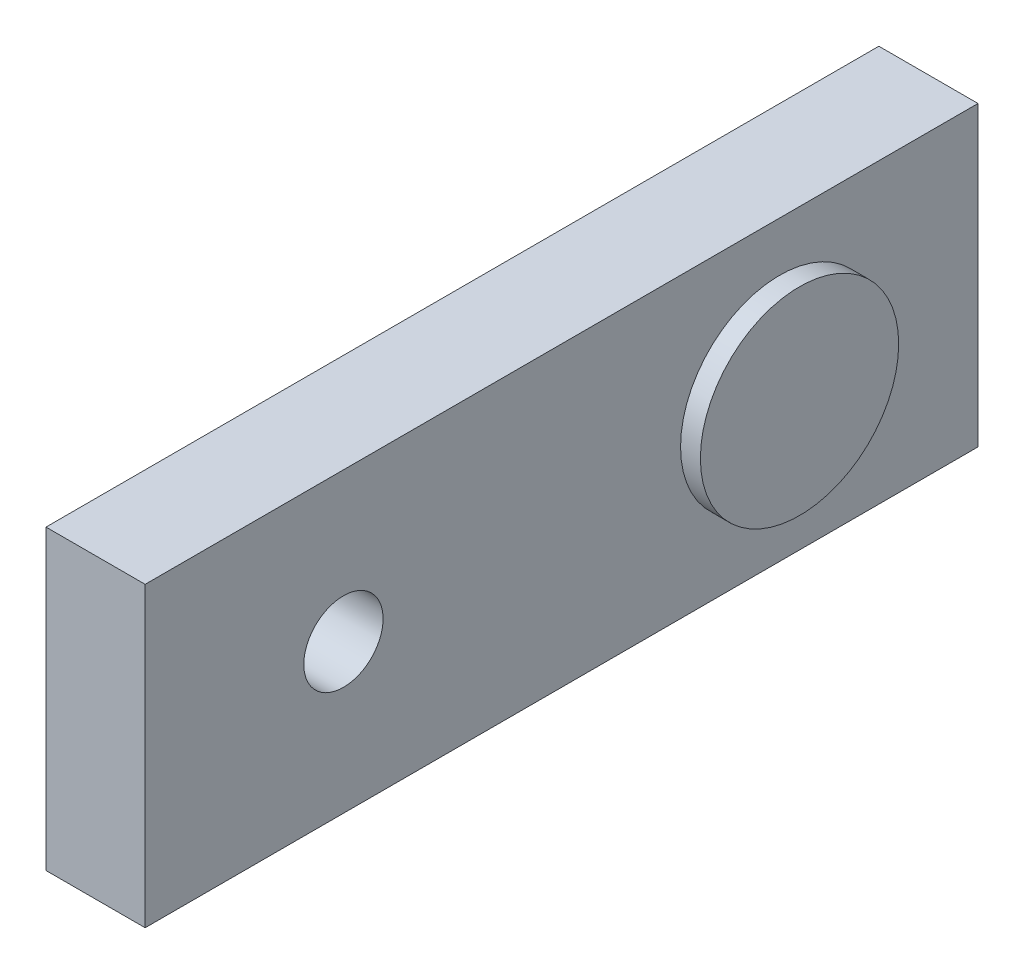
SolidWorks part; units mm, degrees
ref_plane "Front Plane" through (0, 0, 0) normal (0, 0, 1) x (1, 0, 0)
ref_plane "Top Plane" through (0, 0, 0) normal (0, 1, 0) x (1, 0, 0)
ref_plane "Right Plane" through (0, 0, 0) normal (1, 0, 0) x (0, 0, -1)
sketch "Sketch1" plane through (0, 0, 0) normal (0, 0, 1) x (1, 0, 0)
  line L1 (-25, -75) -> (25, -75)
  line L2 (-25, -75) -> (-25, 75)
  line L3 (-25, 75) -> (25, 75)
  line L4 (25, -75) -> (25, 75)
  line L5 (-25, -75) -> (25, 75) construction
  line L6 (-25, 75) -> (25, -75) construction
  point P0 (0, 0)
extrude "Boss-Extrude1" add sketch "Sketch1" along normal blind 420
sketch "Sketch2" plane through (25, 0, 0) normal (1, 0, 0) x (0, 0, -1)
  line L0 (-420, 0) -> (-320, 0) construction
  line L1 (-420, -75) -> (-420, 75) construction
  circle A0 centre (-320, 0) radius 20
extrude "Cut-Extrude1" cut sketch "Sketch2" against normal blind 400 and the other way blind 400
sketch "Sketch3" plane through (25, 0, 0) normal (1, 0, 0) x (0, 0, -1)
  line L0 (0, 0) -> (-100, 0) construction
  line L1 (0, -75) -> (0, 75) construction
  circle A0 centre (-100, 0) radius 50
extrude "Boss-Extrude2" add sketch "Sketch3" along normal blind 10
sketch "Sketch4" plane through (-25, 0, 0) normal (-1, 0, 0) x (0, 0, 1)
  line L0 (0, 0) -> (100, 0) construction
  line L1 (0, 75) -> (0, -75) construction
  circle A0 centre (100, 0) radius 70
sketch "Sketch5" plane through (-25, 0, 0) normal (-1, 0, 0) x (0, 0, 1)
  line L0 (100, 0) -> (320, 0) construction
